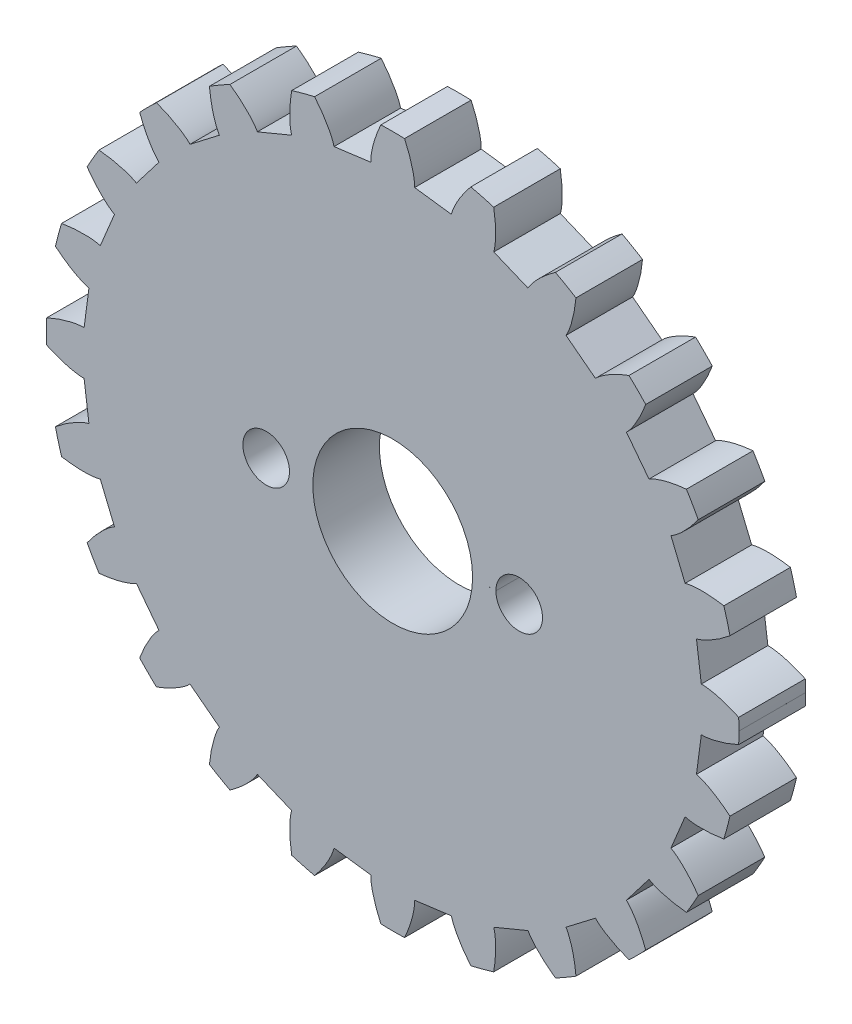
SolidWorks part; units mm, degrees
material "Plain Carbon Steel"
ref_plane "Front Plane" through (0, 0, 0) normal (0, 0, 1) x (1, 0, 0)
ref_plane "Top Plane" through (0, 0, 0) normal (0, 1, 0) x (1, 0, 0)
ref_plane "Right Plane" through (0, 0, 0) normal (1, 0, 0) x (0, 0, -1)
sketch "Sketch1" plane through (0, 0, 0) normal (0, 1, 0) x (1, 0, 0)
  line L0 (0, 0) -> (26, 0)
  line L1 (26, 0) -> (26, -5)
  line L2 (26, -5) -> (0, -5)
  line L3 (0, -5) -> (0, 0)
  line L4 (0, -1) -> (0, -4) construction
  dimension "D1" = 26
  dimension "D2" = 5
revolve "Revolve1" add sketch "Sketch1" angle 360 about L4
sketch "Sketch2" plane through (0, 0, 0) normal (0, 0, 1) x (1, 0, 0)
  spline S0 degree 4 poles (23.177, 1.6482) (23.1813, 1.6485) (23.1935, 1.6491) (23.2164, 1.6496) (23.254, 1.6497) (23.3019, 1.6487) (23.3639, 1.646) (23.437, 1.6411) (23.5174, 1.6339) (23.6049, 1.6241) (23.6923, 1.6126) (23.7796, 1.5995) (23.8665, 1.585) (23.9718, 1.5657) (24.0981, 1.5401) (24.2458, 1.5067) (24.4133, 1.4648) (24.5839, 1.4176) (24.7518, 1.3675) (24.9214, 1.3128) (25.0854, 1.2568) (25.2557, 1.1944) (25.4128, 1.1347) (25.5887, 1.063) (25.7306, 1.0037) (25.9177, 0.9206) (26.028, 0.8699) (26.1572, 0.8089) (26.2145, 0.7809) (26.2497, 0.7637) knots 0 0 0 0 0 0.005377 0.015084 0.028532 0.04661 0.064855 0.092111 0.119476 0.146842 0.174209 0.201575 0.228941 0.256307 0.307035 0.361767 0.4165 0.471232 0.525964 0.580697 0.635429 0.690161 0.744894 0.799626 0.854358 0.909091 0.954545 1 1 1 1 1 construction
  spline S1 degree 4 poles (23.177, 1.6482) (23.1813, 1.6485) (23.1935, 1.6491) (23.2164, 1.6496) (23.254, 1.6497) (23.3019, 1.6487) (23.3639, 1.646) (23.437, 1.6411) (23.5174, 1.6339) (23.6049, 1.6241) (23.6923, 1.6126) (23.7796, 1.5995) (23.8665, 1.585) (23.9718, 1.5657) (24.0981, 1.5401) (24.2458, 1.5067) (24.4133, 1.4648) (24.5839, 1.4176) (24.7518, 1.3675) (24.9214, 1.3128) (25.0854, 1.2568) (25.2557, 1.1944) (25.4128, 1.1347) (25.5887, 1.063) (25.7306, 1.0037) (25.8771, 0.9386) (25.9484, 0.9063) (25.9848, 0.8896) knots 0 0 0 0 0 0.005377 0.015084 0.028532 0.04661 0.064855 0.092111 0.119476 0.146842 0.174209 0.201575 0.228941 0.256307 0.307035 0.361767 0.4165 0.471232 0.525964 0.580697 0.635429 0.690161 0.744894 0.799626 0.854358 0.909091 0.909091 0.909091 0.909091 0.909091
  spline S2 degree 4 poles (22.8139, 4.4066) (22.8181, 4.4075) (22.83, 4.41) (22.8523, 4.4154) (22.8886, 4.4251) (22.9346, 4.4385) (22.9938, 4.4571) (23.0631, 4.4807) (23.1389, 4.5085) (23.221, 4.5406) (23.3024, 4.5744) (23.3833, 4.6096) (23.4635, 4.6461) (23.5602, 4.692) (23.6756, 4.7494) (23.8096, 4.8199) (23.9605, 4.9038) (24.1131, 4.9935) (24.2624, 5.0853) (24.412, 5.1821) (24.556, 5.2786) (24.7043, 5.3829) (24.8406, 5.4813) (24.9919, 5.5961) (25.1137, 5.69) (25.2728, 5.8188) (25.3663, 5.8963) (25.4752, 5.9886) (25.5233, 6.0305) (25.553, 6.0563) knots 0 0 0 0 0 0.005377 0.015084 0.028532 0.04661 0.064855 0.092111 0.119476 0.146842 0.174209 0.201575 0.228941 0.256307 0.307035 0.361767 0.4165 0.471232 0.525964 0.580697 0.635429 0.690161 0.744894 0.799626 0.854358 0.909091 0.954545 1 1 1 1 1 construction
  spline S3 degree 4 poles (22.8139, 4.4066) (22.8181, 4.4075) (22.83, 4.41) (22.8523, 4.4154) (22.8886, 4.4251) (22.9346, 4.4385) (22.9938, 4.4571) (23.0631, 4.4807) (23.1389, 4.5085) (23.221, 4.5406) (23.3024, 4.5744) (23.3833, 4.6096) (23.4635, 4.6461) (23.5602, 4.692) (23.6756, 4.7494) (23.8096, 4.8199) (23.9605, 4.9038) (24.1131, 4.9935) (24.2624, 5.0853) (24.412, 5.1821) (24.556, 5.2786) (24.7043, 5.3829) (24.8406, 5.4813) (24.9919, 5.5961) (25.1137, 5.69) (25.2383, 5.7909) (25.2988, 5.8405) (25.3296, 5.8661) knots 0 0 0 0 0 0.005377 0.015084 0.028532 0.04661 0.064855 0.092111 0.119476 0.146842 0.174209 0.201575 0.228941 0.256307 0.307035 0.361767 0.4165 0.471232 0.525964 0.580697 0.635429 0.690161 0.744894 0.799626 0.854358 0.909091 0.909091 0.909091 0.909091 0.909091
  spline S4 degree 4 poles (22.7775, 4.6829) (22.7807, 4.6587) (22.7869, 4.6115) (22.7943, 4.5548) (22.8117, 4.4234) (22.8198, 4.3613) (22.8431, 4.1843) (22.8567, 4.0812) (22.8772, 3.9253) (22.894, 3.798) (22.9128, 3.6552) (22.9298, 3.5256) (22.9476, 3.3909) (22.9638, 3.2678) (22.9809, 3.1377) (22.9981, 3.0069) (23.0161, 2.8701) (23.0345, 2.7307) (23.0532, 2.5884) (23.0711, 2.4528) (23.0907, 2.3041) (23.1075, 2.1759) (23.1295, 2.009) (23.1444, 1.8957) (23.1712, 1.6924) (23.1801, 1.6248) (23.1989, 1.4819) (23.2062, 1.4268) (23.211, 1.39) (23.2135, 1.371) knots 0 0 0 0 0 0.028849 0.052878 0.083333 0.124324 0.163161 0.206806 0.246995 0.288912 0.331781 0.370109 0.409255 0.448242 0.482806 0.525716 0.568843 0.611704 0.653696 0.694186 0.738248 0.782176 0.823818 0.871169 0.916667 0.958584 0.979292 1 1 1 1 1 construction
  spline S5 degree 4 poles (22.8139, 4.4066) (22.8176, 4.3783) (22.8244, 4.3263) (22.8431, 4.1843) (22.8567, 4.0812) (22.8772, 3.9253) (22.894, 3.798) (22.9128, 3.6552) (22.9298, 3.5256) (22.9476, 3.3909) (22.9638, 3.2678) (22.9809, 3.1377) (22.9981, 3.0069) (23.0161, 2.8701) (23.0345, 2.7307) (23.0532, 2.5884) (23.0711, 2.4528) (23.0907, 2.3041) (23.1075, 2.1759) (23.1295, 2.009) (23.1444, 1.8957) (23.1648, 1.7407) (23.1729, 1.6796) (23.177, 1.6482) knots 0.083333 0.083333 0.083333 0.083333 0.083333 0.124324 0.163161 0.206806 0.246995 0.288912 0.331781 0.370109 0.409255 0.448242 0.482806 0.525716 0.568843 0.611704 0.653696 0.694186 0.738248 0.782176 0.823818 0.871169 0.916667 0.916667 0.916667 0.916667 0.916667
  spline S6 degree 4 poles (22.5838, 0.7731) (23.0672, 0.7897) (23.6703, 0.8103) (25.5078, 0.8732) (26.4501, 0.9055) (28.7534, 0.9843) (30.1565, 1.0324) (32.1757, 1.1015) (33.8803, 1.1599) (35.8485, 1.2272) (37.6947, 1.2904) (39.6506, 1.3574) (41.5311, 1.4218) (43.4321, 1.4869) (45.2708, 1.5498) (47.0129, 1.6094) (48.7163, 1.6678) (50.2285, 1.7195) (51.6384, 1.7678) (52.9613, 1.8131) (54.2605, 1.8576) (55.4506, 1.8983) (56.8677, 1.9468) (57.8956, 1.982) (59.7111, 2.0441) (60.37, 2.0667) (62.0621, 2.1246) (62.6297, 2.1441) (63.1349, 2.1614) (63.3918, 2.1702) knots 0 0 0 0 0 0.041667 0.083333 0.123541 0.166753 0.209392 0.256181 0.300395 0.346612 0.394832 0.44205 0.489269 0.53291 0.580271 0.622911 0.660113 0.699653 0.729462 0.759701 0.79242 0.822588 0.854043 0.885331 0.916667 0.957078 0.978539 1 1 1 1 1 construction
  spline S7 degree 4 poles (25.9848, 0.8896) (26.3263, 0.9013) (27.0223, 0.9251) (28.7534, 0.9843) (30.1565, 1.0324) (32.1757, 1.1015) (33.8803, 1.1599) (35.8485, 1.2272) (37.6947, 1.2904) (39.6506, 1.3574) (41.5311, 1.4218) (43.4321, 1.4869) (45.2708, 1.5498) (47.0129, 1.6094) (48.7163, 1.6678) (50.2285, 1.7195) (51.6384, 1.7678) (52.9613, 1.8131) (54.2605, 1.8576) (55.4506, 1.8983) (56.8677, 1.9468) (57.8956, 1.982) (59.1656, 2.0255) (59.6986, 2.0437) (59.9648, 2.0528) knots 0.083333 0.083333 0.083333 0.083333 0.083333 0.123541 0.166753 0.209392 0.256181 0.300395 0.346612 0.394832 0.44205 0.489269 0.53291 0.580271 0.622911 0.660113 0.699653 0.729462 0.759701 0.79242 0.822588 0.854043 0.885331 0.916667 0.916667 0.916667 0.916667 0.916667
  spline S8 degree 4 poles (59.9935, 0.8853) (59.9921, 0.9686) (59.9891, 1.1296) (59.9859, 1.3474) (59.9691, 1.9373) (59.9603, 2.1956) (59.9292, 2.9561) (59.9042, 3.3875) (59.8676, 4.0111) (59.8299, 4.5186) (59.7847, 5.0956) (59.7358, 5.63) (59.6811, 6.1892) (59.6218, 6.733) (59.5573, 7.2845) (59.4875, 7.8317) (59.4133, 8.3783) (59.3328, 8.9276) (59.2494, 9.4683) (59.1575, 10.0226) (59.0664, 10.5515) (58.9607, 11.1205) (58.8658, 11.6204) (58.7398, 12.2323) (58.6522, 12.6554) (58.4855, 13.3981) (58.4271, 13.6498) (58.2906, 14.224) (58.2374, 14.4352) (58.1986, 14.5915) (58.1784, 14.6723) knots 0 0 0 0 0 0.020959 0.041918 0.083333 0.123016 0.162698 0.202381 0.242063 0.281746 0.321429 0.361111 0.400794 0.440476 0.480159 0.519841 0.559524 0.599206 0.638889 0.678571 0.718254 0.757937 0.797619 0.837302 0.876984 0.916667 0.958082 0.979041 1 1 1 1 1 construction
  spline S9 degree 4 poles (59.9648, 2.0528) (59.9608, 2.1679) (59.9523, 2.3919) (59.9292, 2.9561) (59.9042, 3.3875) (59.8676, 4.0111) (59.8299, 4.5186) (59.7847, 5.0956) (59.7358, 5.63) (59.6811, 6.1892) (59.6218, 6.733) (59.5573, 7.2845) (59.4875, 7.8317) (59.4133, 8.3783) (59.3328, 8.9276) (59.2494, 9.4683) (59.1575, 10.0226) (59.0664, 10.5515) (58.9607, 11.1205) (58.8658, 11.6204) (58.7398, 12.2323) (58.6522, 12.6554) (58.5285, 13.2064) (58.4788, 13.425) (58.4528, 13.5371) knots 0.083333 0.083333 0.083333 0.083333 0.083333 0.123016 0.162698 0.202381 0.242063 0.281746 0.321429 0.361111 0.400794 0.440476 0.480159 0.519841 0.559524 0.599206 0.638889 0.678571 0.718254 0.757937 0.797619 0.837302 0.876984 0.916667 0.916667 0.916667 0.916667 0.916667
  spline S10 degree 4 poles (61.7739, 14.3063) (61.7039, 14.2901) (61.5796, 14.2613) (61.4666, 14.2351) (60.8505, 14.0924) (60.4206, 13.9929) (58.8446, 13.6279) (58.2932, 13.5002) (56.7254, 13.1371) (55.8234, 12.9282) (54.568, 12.6374) (53.4429, 12.3769) (52.0511, 12.0546) (50.5992, 11.7183) (49.0504, 11.3596) (47.4563, 10.9905) (45.8632, 10.6215) (44.3102, 10.2618) (42.7618, 9.9032) (41.1907, 9.5394) (39.6063, 9.1725) (38.0428, 8.8104) (36.385, 8.4264) (34.8232, 8.0647) (33.0593, 7.6562) (31.5267, 7.3013) (29.6304, 6.8621) (28.2966, 6.5532) (25.8856, 5.9949) (25.0823, 5.8088) (23.5273, 5.4487) (22.7343, 5.2651) (22.3407, 5.1739) (22.1153, 5.1217) (22.0166, 5.0988) knots 0 0 0 0 0 0.005334 0.010668 0.021335 0.042671 0.083333 0.112698 0.136843 0.163043 0.191355 0.228657 0.25743 0.298405 0.34029 0.382676 0.419052 0.457933 0.497208 0.537818 0.578079 0.616034 0.656645 0.70114 0.741113 0.784 0.826386 0.866769 0.916667 0.958333 0.979167 0.989583 1 1 1 1 1 construction
  spline S11 degree 4 poles (58.4528, 13.5371) (58.2096, 13.4808) (57.7636, 13.3775) (56.7254, 13.1371) (55.8234, 12.9282) (54.568, 12.6374) (53.4429, 12.3769) (52.0511, 12.0546) (50.5992, 11.7183) (49.0504, 11.3596) (47.4563, 10.9905) (45.8632, 10.6215) (44.3102, 10.2618) (42.7618, 9.9032) (41.1907, 9.5394) (39.6063, 9.1725) (38.0428, 8.8104) (36.385, 8.4264) (34.8232, 8.0647) (33.0593, 7.6562) (31.5267, 7.3013) (29.6304, 6.8621) (28.2966, 6.5532) (26.4619, 6.1283) (25.7428, 5.9618) (25.3296, 5.8661) knots 0.083333 0.083333 0.083333 0.083333 0.083333 0.112698 0.136843 0.163043 0.191355 0.228657 0.25743 0.298405 0.34029 0.382676 0.419052 0.457933 0.497208 0.537818 0.578079 0.616034 0.656645 0.70114 0.741113 0.784 0.826386 0.866769 0.916667 0.916667 0.916667 0.916667 0.916667
extrude "Cut-Extrude2" cut sketch "Sketch2" against normal blind 6 and the other way blind 6
ref_axis "Axis1" through (0, 0, -0.25) along (0, 0, 1)
pattern_circular "CirPattern2" count 24 over 360 about axis through (0, 0, 5) along (0, 0, -1) of "Cut-Extrude2"
sketch "Sketch3" plane through (0, 0, 0) normal (0, 0, 1) x (1, 0, 0)
  circle A0 centre (0, 0) radius 6
  circle A1 centre (9.5, 0) radius 1.75
  circle A2 centre (-9.5, 0) radius 1.75
  dimension "D1" = 12
  dimension "D3" = 3.5
  dimension "D5" = 3.5
  dimension "D2" = 9.5
  dimension "D4" = 9.5
extrude "Cut-Extrude4" cut sketch "Sketch3" against normal blind 7 and the other way blind 7
equation "\"TrigProbe\"= cos(60)"
equation "\"SqrProbe\"= sqr(2)"
equation "\"AtnProbe\"= atn(1)"
equation "\"ToothCount\" = 24"
equation "\"DP\"= 12.7"
equation "\"PA\"= 14.5"
equation "\"PArad\"= \"PA\" * 3.14159265358979 / 180"
equation "\"Rb\"= \"ToothCount\" / \"DP\" * cos(\"PA\") / 2"
equation "\"Ra\"= (\"ToothCount\" + 2) / \"DP\" / 2"
equation "\"Tmax\"= sqr(\"Ra\" * \"Ra\" / (\"Rb\" * \"Rb\") - 1)"
equation "\"Delta\"= 3.14159265358979 / (2 * \"ToothCount\") + tan(\"PA\") - \"PArad\""
equation "\"Gamma\"= 2 * 3.14159265358979 / \"ToothCount\""
equation "\"ThetaL\"= atn(\"Tmax\") * 3.14159265358979 / 180 - \"Tmax\" + \"Delta\""
equation "\"ThetaU\"= \"Tmax\" - atn(\"Tmax\") * 3.14159265358979 / 180 - \"Delta\" + \"Gamma\""
equation "\"D1@Sketch1\" = \"Ra\""
equation "\"D1@CirPattern2\" = \"ToothCount\""
